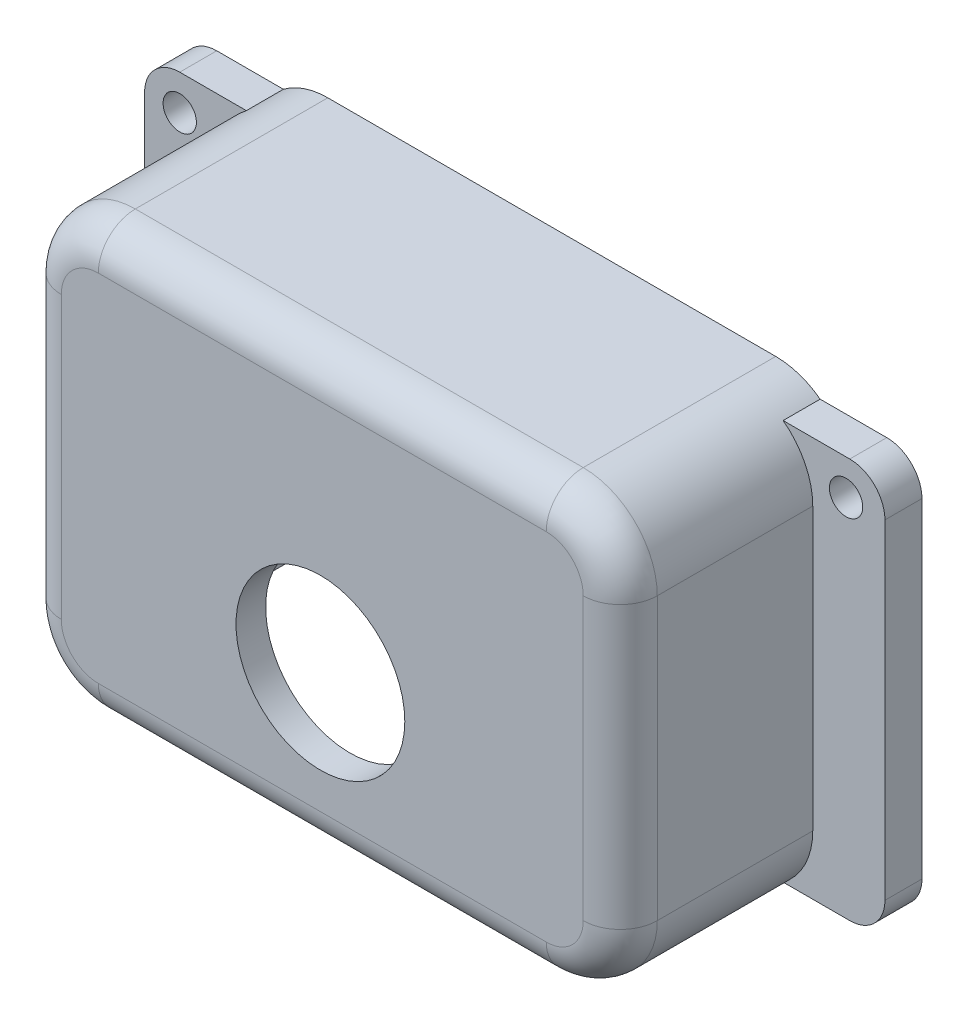
SolidWorks part; units mm, degrees
ref_plane "Alzado" through (0, 0, 0) normal (0, 0, 1) x (1, 0, 0)
ref_plane "Planta" through (0, 0, 0) normal (0, 1, 0) x (1, 0, 0)
ref_plane "Vista lateral" through (0, 0, 0) normal (1, 0, 0) x (0, 0, -1)
sketch "Croquis1" plane through (0, 0, 0) normal (0, 0, 1) x (1, 0, 0)
  line L0 (40.25, 29) -> (40.25, -29)
  line L1 (-45.25, 27) -> (45.25, 27)
  line L2 (-50, 22.25) -> (-50, -22.25)
  line L3 (-45.25, -27) -> (45.25, -27)
  line L4 (50, 22.25) -> (50, -22.25)
  line L5 (-50, 27) -> (50, -27) construction
  line L6 (-50, -27) -> (50, 27) construction
  line L7 (-35.25, 24) -> (35.25, 24)
  line L8 (-35.25, 24) -> (-35.25, -24)
  line L9 (-35.25, -24) -> (35.25, -24)
  line L10 (35.25, 24) -> (35.25, -24)
  line L11 (-35.25, 24) -> (35.25, -24) construction
  line L12 (-35.25, -24) -> (35.25, 24) construction
  line L13 (-40.25, -29) -> (40.25, -29)
  line L14 (-40.25, 29) -> (-40.25, -29)
  line L15 (-40.25, 29) -> (40.25, 29)
  arc A0 (-50, -22.25) -> (-45.25, -27) centre (-45.25, -22.25) ccw
  arc A1 (45.25, -27) -> (50, -22.25) centre (45.25, -22.25) ccw
  arc A2 (45.25, 27) -> (50, 22.25) centre (45.25, 22.25) cw
  arc A3 (-45.25, 27) -> (-50, 22.25) centre (-45.25, 22.25) ccw
  circle A4 centre (-45.25, 22.25) radius 2.25
  circle A5 centre (44.75, 22.25) radius 2.25
  point P0 (0, 0)
  point P18 (0, 0)
  dimension "D3" = 4.75
  dimension "D1" = 100
  dimension "D2" = 54
  dimension "D4" = 14.75
  dimension "D5" = 3
  dimension "D6" = 5
extrude "Saliente-Extruir1" add sketch "Croquis1" along normal blind 5 contours L1 A3 L2 A0 L3 L14 | A2 L1 L0 L3 A1 L4 | L1 L14 L3 L0 L7 L10 L9 L8 region at (45.0632, -0.7065, 0) region at (39.2807, 0, 0) region at (-45.0473, -0.7065, 0)
extrude "Saliente-Extruir2" add sketch "Croquis1<3>" along normal blind 31 contours L10 L7 L8 L9 | L15 L14 L1 L0 | L1 L14 L3 L0 L7 L10 L9 L8 | L3 L14 L13 L0 region at (0, 28, 0) region at (39.2807, 0, 0) region at (0, -28, 0) region at (0, 0, 0)
sketch "Croquis1<3>" plane through (0, 0, 0) normal (0, 0, 1) x (1, 0, 0) same geometry as "Croquis1"
extrude "Cortar-Extruir2" cut sketch "Croquis1<5>" along normal blind 27 contours L10 L7 L8 L9 region at (0, 0, 0)
sketch "Croquis1<5>" plane through (0, 0, 0) normal (0, 0, 1) x (1, 0, 0) same geometry as "Croquis1"
fillet "Redondeo4" radius 5 4 edges at (0, -29, 31) (-40.25, 0, 31) (0, 29, 31) (40.25, 0, 31)
fillet "Redondeo5" radius 10 8 edges at (38.7855, 27.5355, 29.5355) (-38.7855, 27.5355, 29.5355) (-38.7855, -27.5355, 29.5355) (38.7855, -27.5355, 29.5355) (40.25, -29, 13) (-40.25, -29, 13) (-40.25, 29, 13) (40.25, 29, 13)
sketch "Croquis3" plane through (0, -24, 0) normal (0, 1, 0) x (1, 0, 0)
  line L4 (35.25, 0) -> (-35.25, 0)
  line L5 (-35.25, 0) -> (-35.25, -27)
  line L6 (-35.25, -27) -> (35.25, -27)
  line L7 (35.25, -27) -> (35.25, 0)
  line L8 (35.25, 0) -> (-35.25, 0)
  line L9 (-35.25, 0) -> (-35.25, -27)
  line L10 (-35.25, -27) -> (35.25, -27)
  line L11 (35.25, -27) -> (35.25, 0)
  dimension "D1" = 0
extrude "Cortar-Extruir5" cut sketch "Croquis3" against normal through all
sketch "Croquis4" plane through (0, 0, 31) normal (0, 0, 1) x (1, 0, 0)
  line L0 (-30.25, -24) -> (30.25, -24) construction
  circle A0 centre (-0.25, -7.75) radius 11.4
  dimension "D1" = 22.8
  dimension "D2" = 16.25
extrude "Cortar-Extruir6" cut sketch "Croquis4" against normal blind 10
